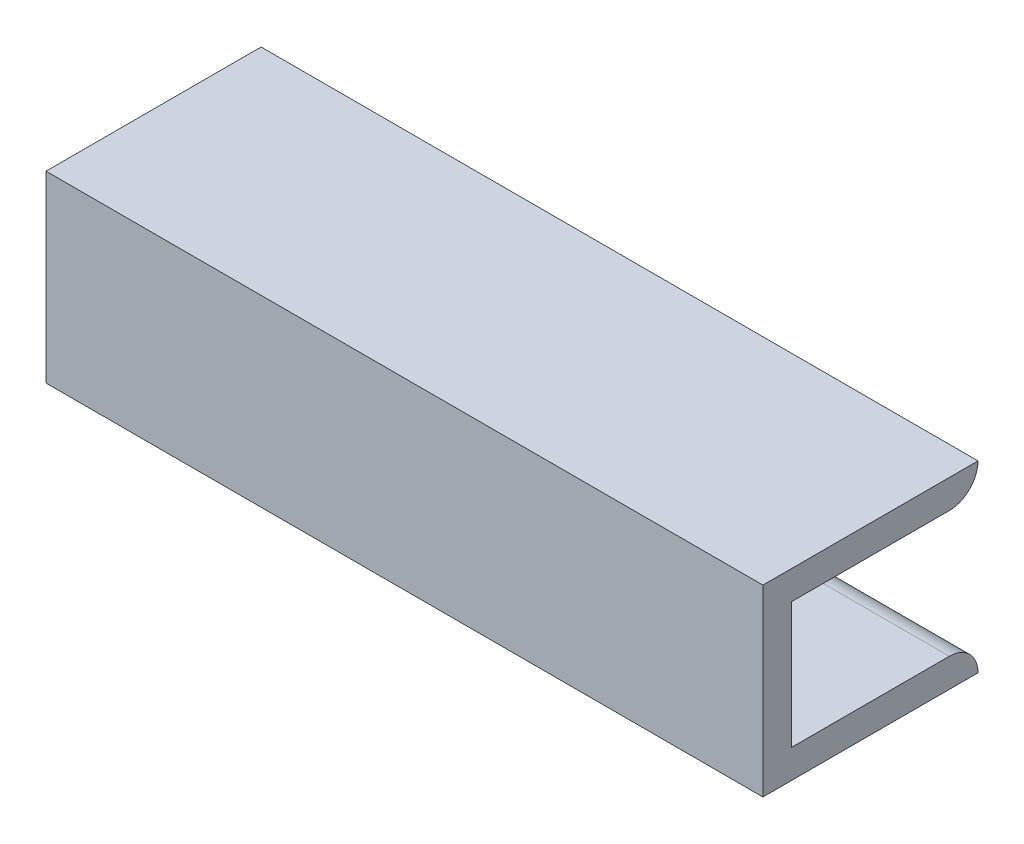
SolidWorks part; units mm, degrees
ref_plane "前视基准面" through (0, 0, 0) normal (0, 0, 1) x (1, 0, 0)
ref_plane "上视基准面" through (0, 0, 0) normal (0, 1, 0) x (1, 0, 0)
ref_plane "右视基准面" through (0, 0, 0) normal (1, 0, 0) x (0, 0, -1)
sketch "草图1" plane through (0, 0, 0) normal (0, 0, 1) x (1, 0, 0)
  line L1 (0, 0) -> (50, 0)
  line L2 (0, 0) -> (0, -2)
  line L3 (0, -2) -> (50, -2)
  line L4 (50, 0) -> (50, -2)
  line L5 (0, 8.8) -> (50, 8.8)
  line L6 (0, 8.8) -> (0, 10.8)
  line L7 (0, 10.8) -> (50, 10.8)
  line L8 (50, 8.8) -> (50, 10.8)
  point P9 (0, 9.8)
  dimension "D1" = 2
  dimension "D2" = 2
  dimension "D3" = 8.8
  dimension "D4" = 50
extrude "凸台-拉伸1" add sketch "草图1" along normal blind 15
sketch "草图2" plane through (0, 0, 15) normal (0, 0, 1) x (1, 0, 0)
  line L1 (0, -2) -> (50, -2)
  line L2 (0, -2) -> (0, 10.8)
  line L3 (0, 10.8) -> (50, 10.8)
  line L4 (50, -2) -> (50, 10.8)
extrude "凸台-拉伸2" add sketch "草图2" against normal blind 2
fillet "圆角1" radius 2 2 edges at (25, 0, 0) (25, 8.8, 0)
